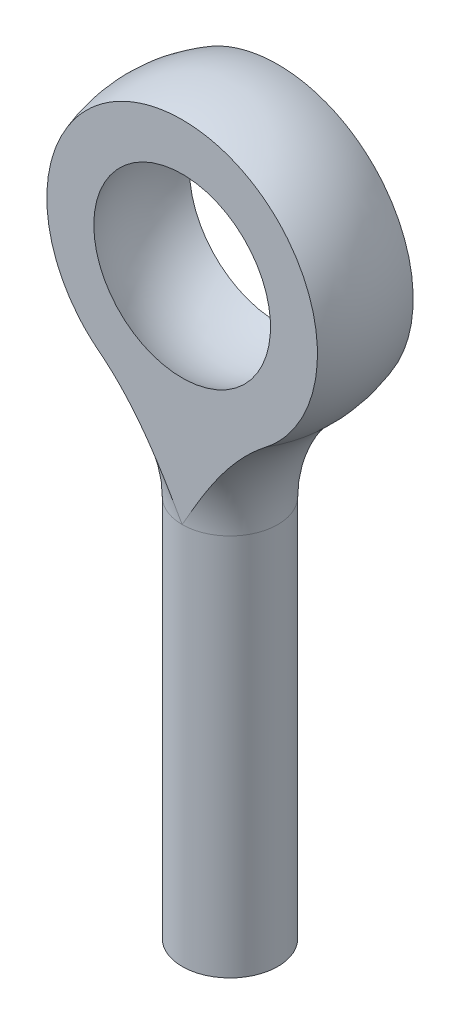
SolidWorks part; units mm, degrees
material "Alloy Steel"
ref_plane "Front Plane" through (0, 0, 0) normal (0, 0, 1) x (1, 0, 0)
ref_plane "Top Plane" through (0, 0, 0) normal (0, 1, 0) x (1, 0, 0)
ref_plane "Right Plane" through (0, 0, 0) normal (1, 0, 0) x (0, 0, -1)
sketch "Sketch2" plane through (0, 0, 0) normal (0, 0, 1) x (1, 0, 0)
  line L0 (0, -14.2875) -> (0, -39.6875)
  line L1 (0, -39.6875) -> (3.175, -39.6875)
  line L2 (3.175, -39.6875) -> (3.175, -14.2875)
  line L3 (3.175, -14.2875) -> (0, -14.2875)
  line L5 (0, 9.525) -> (0, -14.2875)
  line L6 (0, 9.525) -> (9.525, 9.525) construction
  line L7 (9.525, 9.525) -> (9.525, 0) construction
  line L8 (-3.175, -39.6875) -> (-3.175, -14.2875) construction
  line L9 (3.2732, -39.6308) -> (3.2732, -40.5376)
  line L10 (3.2732, -40.5376) -> (2.4879, -40.0842)
  line L11 (2.586, -40.1409) -> (2.586, -40.0275)
  line L12 (2.4879, -40.0842) -> (3.2732, -39.6308)
  line L13 (3.2241, -39.6592) -> (3.2241, -40.5093)
  line L14 (3.2732, -40.0842) -> (3.175, -40.0842)
  line L15 (3.175, -39.6875) -> (3.175, -40.4809)
  line L16 (2.4879, -40.0842) -> (2.586, -40.0842)
  arc A0 (6.3827, -7.0701) -> (0, 9.525) centre (0, 0) ccw
  circle A1 centre (0, 0) radius 3.175 construction
  circle A2 centre (0, 0) radius 6.35 construction
  circle A3 centre (0, 0) radius 6.604 construction
  arc A4 (3.175, -14.2875) -> (6.3827, -7.0701) centre (12.8984, -14.2875) cw
  point P24 (0, 6.35)
  point P26 (3.175, -40.0842)
  point P28 (3.2241, -40.0842)
  dimension "D1" = 13.208
  dimension "A" = 6.35
  dimension "Ball Dia" = 12.7
  dimension "B" = 19.05
  dimension "D" = 39.6875
  dimension "E" = 25.4
  dimension "Thread Dia" = 3.175
  dimension "D2" = 60
  dimension "Pitch" = 0.9068
  dimension "D4" = 0.1133
revolve "Revolve1" add sketch "Sketch2" angle 360 about L5 region at (1.5875, -26.9875, 0) region at (3.8039, -1.3646, 0)
sketch "Sketch3" plane through (0, 0, 0) normal (1, 0, 0) x (0, 0, -1)
  line L0 (-3.175, -14.2875) -> (-3.175, 10.7125)
  line L1 (-3.175, 10.7125) -> (-11.175, 10.7125)
  line L2 (-11.175, 10.7125) -> (-11.175, -14.2875)
  line L3 (-11.175, -14.2875) -> (-3.175, -14.2875)
  line L4 (0, 0) -> (0, -14.2875)
  line L5 (11.175, 10.7125) -> (11.175, -14.2875)
  line L6 (3.175, 10.7125) -> (11.175, 10.7125)
  line L7 (3.175, -14.2875) -> (3.175, 10.7125)
  line L8 (11.175, -14.2875) -> (3.175, -14.2875)
  arc A0 (-3.175, -14.2875) -> (-6.3827, -7.0701) centre (-12.8984, -14.2875) ccw construction
  dimension "D1" = 25
  dimension "D2" = 8
extrude "Cut-Extrude1" cut sketch "Sketch3" against normal through all both and the other way through all contours L2 L3 L0 L1 | L8 L5 L6 L7 region at (0, -1.7875, 7.175) region at (0, -1.7875, -7.175)
sketch "Sketch4" plane through (0, 0, 0) normal (0, 0, 1) x (1, 0, 0)
  line L0 (0, 0) -> (0, 6.6675)
  line L1 (0, 0) -> (0, -6.6675)
  line L2 (0, 0) -> (0, -14.2875)
  circle A0 centre (0, 0) radius 6.6675
  dimension "D1" = 13.335
revolve "Cut-Revolve2" cut sketch "Sketch4" angle 360 about L2 region at (-2.8298, 0, 0)
sketch "Sketch5" plane through (0, 0, 0) normal (0, 0, 1) x (1, 0, 0)
  line L0 (0, 0) -> (0, 6.35)
  line L1 (0, 0) -> (0, -6.35)
  circle A0 centre (0, 0) radius 6.35
  dimension "D1" = 12.7
revolve "Revolve7" [suppressed] add sketch "Sketch5" angle 360 about L1
sketch "Sketch6" plane through (0, 0, 0) normal (0, 0, 1) x (1, 0, 0)
  circle A0 centre (0, 0) radius 3.175
  dimension "D1" = 6.35
extrude "Cut-Extrude2" [suppressed] cut sketch "Sketch6" against normal through all both and the other way through all contours A0
chamfer "Chamfer1" [suppressed] distance 0.635 angle 45
